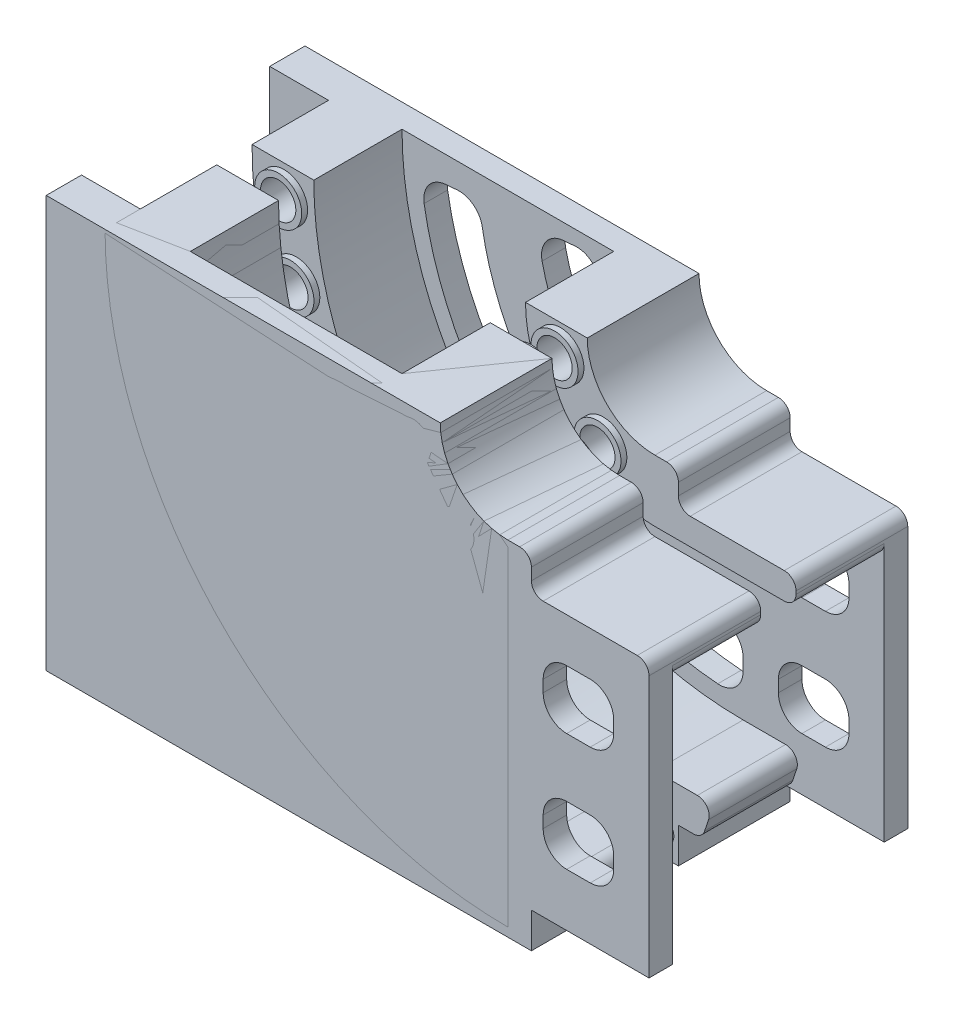
SolidWorks part; units mm, degrees
ref_plane "前视基准面" through (0, 0, 0) normal (0, 0, 1) x (1, 0, 0)
ref_plane "上视基准面" through (0, 0, 0) normal (0, 1, 0) x (1, 0, 0)
ref_plane "右视基准面" through (0, 0, 0) normal (1, 0, 0) x (0, 0, -1)
other "Configuration Table"
sketch "草图1" plane through (0, 0, 0) normal (0, 0, 1) x (1, 0, 0)
  line L0 (0, 0) -> (0, -1)
  arc A0 (0, -1) -> (20, -21) centre (20, -1) ccw
  dimension "D1" = 20
  dimension "D2" = 1
sketch "草图2" plane through (0, 0, 0) normal (0, 1, 0) x (1, 0, 0)
  line L1 (-9, -9) -> (9, -9)
  line L2 (-9, -9) -> (-9, 9)
  line L3 (-9, 9) -> (9, 9)
  line L4 (9, -9) -> (9, 9)
  line L5 (-9, -9) -> (9, 9) construction
  line L6 (-9, 9) -> (9, -9) construction
  line L7 (-14.25, -11) -> (14.25, -11)
  line L8 (-14.25, -11) -> (-14.25, 11)
  line L9 (-14.25, 11) -> (14.25, 11)
  line L10 (14.25, -11) -> (14.25, 11)
  line L11 (-14.25, -11) -> (14.25, 11) construction
  line L12 (-14.25, 11) -> (14.25, -11) construction
  point P0 (0, 0)
  point P6 (0, 0)
  dimension "D1" = 2
  dimension "D2" = 18
  dimension "D3" = 5.25
sweep "扫描1" add profiles "草图2" path "草图1"
sketch "草图3" plane through (0, 0, 0) normal (0, 1, 0) x (1, 0, 0)
  line L1 (-16.4922, 1.5) -> (34.5235, 1.5)
  line L2 (-16.4922, 1.5) -> (-16.4922, -1.5)
  line L3 (-16.4922, -1.5) -> (34.5235, -1.5)
  line L4 (34.5235, 1.5) -> (34.5235, -1.5)
  dimension "D1" = 3
  dimension "1" = 1.5
extrude "切除-拉伸1" cut sketch "草图3" against normal blind 50
sketch "草图5" plane through (0, 0, -1.5) normal (0, 0, 1) x (1, 0, 0)
  line L0 (20, -12) -> (20, -6.75) construction
  line L1 (12.1, 0) -> (-12.1, 0) construction
  line L2 (20, -35.25) -> (20, -30) construction
  line L3 (-11.625, -1) -> (-11.625, 0) construction
  line L8 (14.25, 0) -> (9, 0)
  line L9 (9, 0) -> (9, -1)
  line L10 (20, -12) -> (20, -6.75)
  line L11 (14.25, -1) -> (14.25, 0)
  line L12 (14.25, 0) -> (9, 0)
  line L13 (9, 0) -> (9, -1)
  line L14 (20, -12) -> (20, -6.75)
  line L15 (14.25, -1) -> (14.25, 0)
  line L16 (20, -35.25) -> (20, -30)
  line L17 (-9, -1) -> (-9, 0)
  line L18 (-9, 0) -> (-14.25, 0)
  line L19 (-14.25, 0) -> (-14.25, -1)
  line L20 (20, -35.25) -> (20, -30)
  line L21 (-9, -1) -> (-9, 0)
  line L22 (-9, 0) -> (-14.25, 0)
  line L23 (-14.25, 0) -> (-14.25, -1)
  arc A0 (20, -9.375) -> (11.6849, 0) centre (20, -1) cw construction
  arc A1 (14.25, -1) -> (20, -6.75) centre (20, -1) ccw construction
  arc A2 (20, -32.625) -> (-11.625, -1) centre (20, -1) cw construction
  circle A3 centre (11.9674, -3.3702) radius 3 construction
  circle A4 centre (15.6141, -8.1348) radius 3 construction
  circle A5 centre (21.5119, -9.2374) radius 3 construction
  circle A6 centre (26.6337, -6.1121) radius 3 construction
  circle A7 centre (28.3507, -0.3631) radius 3 construction
  circle A8 centre (11.9674, -3.3702) radius 1.5
  circle A9 centre (15.6141, -8.1348) radius 1.5
  circle A10 centre (21.5119, -9.2374) radius 1.5
  circle A11 centre (26.6337, -6.1121) radius 1.5
  circle A12 centre (28.3507, -0.3631) radius 1.5
  circle A13 centre (-11.5273, -3.484) radius 3 construction
  circle A14 centre (-10.4907, -9.3938) radius 3 construction
  circle A15 centre (-8.3567, -15.0014) radius 3 construction
  circle A16 centre (-5.2019, -20.1051) radius 3 construction
  circle A17 centre (-1.14, -24.5211) radius 3 construction
  circle A18 centre (3.6829, -28.0904) radius 3 construction
  circle A19 centre (9.093, -30.6847) radius 3 construction
  circle A20 centre (14.8958, -32.2104) radius 3 construction
  circle A21 centre (20.8823, -32.6127) radius 3 construction
  circle A22 centre (26.837, -31.8771) radius 3 construction
  circle A23 centre (32.5457, -30.0301) radius 3 construction
  circle A24 centre (-11.5273, -3.484) radius 1.5
  circle A25 centre (-10.4907, -9.3938) radius 1.5
  arc A26 (9, -1) -> (20, -12) centre (20, -1) ccw
  arc A27 (14.25, -1) -> (20, -6.75) centre (20, -1) ccw
  arc A28 (9, -1) -> (20, -12) centre (20, -1) ccw
  arc A29 (14.25, -1) -> (20, -6.75) centre (20, -1) ccw
  arc A30 (-14.25, -1) -> (20, -35.25) centre (20, -1) ccw
  arc A31 (-9, -1) -> (20, -30) centre (20, -1) ccw
  arc A32 (-14.25, -1) -> (20, -35.25) centre (20, -1) ccw
  arc A33 (-9, -1) -> (20, -30) centre (20, -1) ccw
  circle A34 centre (-8.3567, -15.0014) radius 1.5
  circle A35 centre (-5.2019, -20.1051) radius 1.5
  circle A36 centre (-1.14, -24.5211) radius 1.5
  circle A37 centre (3.6829, -28.0904) radius 1.5
  circle A38 centre (9.093, -30.6847) radius 1.5
  circle A39 centre (14.8958, -32.2104) radius 1.5
  circle A40 centre (20.8823, -32.6127) radius 1.5
  circle A41 centre (26.837, -31.8771) radius 1.5
  circle A42 centre (32.5457, -30.0301) radius 1.5
  circle A43 centre (11.9674, -3.3702) radius 2
  circle A44 centre (15.6141, -8.1348) radius 2
  circle A45 centre (21.5119, -9.2374) radius 2
  circle A46 centre (26.6337, -6.1121) radius 2
  circle A47 centre (28.3507, -0.3631) radius 2
  circle A48 centre (32.5457, -30.0301) radius 2
  circle A49 centre (26.837, -31.8771) radius 2
  circle A50 centre (20.8823, -32.6127) radius 2
  circle A51 centre (14.8958, -32.2104) radius 2
  circle A52 centre (9.093, -30.6847) radius 2
  circle A53 centre (3.6829, -28.0904) radius 2
  circle A54 centre (-1.14, -24.5211) radius 2
  circle A55 centre (-5.2019, -20.1051) radius 2
  circle A56 centre (-8.3567, -15.0014) radius 2
  circle A57 centre (-10.4907, -9.3938) radius 2
  circle A58 centre (-11.5273, -3.484) radius 2
  dimension "D1" = 6
  dimension "D4" = 3
  dimension "D5" = 4
  dimension "D2" = 0
  dimension "D3" = 0
extrude "凸台-拉伸1" add sketch "草图5" along normal blind 0.5 contours A58 A24 | A43 A8 | A44 A9 | A51 A39 | A52 A38 | A53 A37 | A54 A36 | A55 A35 | A56 A34 | A57 A25 | A12
sketch "草图7" plane through (0, 0, -1.5) normal (0, 0, 1) x (1, 0, 0)
  circle A0 centre (11.9674, -3.3702) radius 1.5 construction
  circle A1 centre (15.6141, -8.1348) radius 1.5 construction
  circle A8 centre (14.8958, -32.2104) radius 1.5 construction
  circle A9 centre (9.093, -30.6847) radius 1.5 construction
  circle A10 centre (3.6829, -28.0904) radius 1.5 construction
  circle A11 centre (-1.14, -24.5211) radius 1.5 construction
  circle A12 centre (-5.2019, -20.1051) radius 1.5 construction
  circle A13 centre (-8.3567, -15.0014) radius 1.5 construction
  circle A14 centre (-10.4907, -9.3938) radius 1.5 construction
  circle A15 centre (-11.5273, -3.484) radius 1.5 construction
  circle A16 centre (11.9674, -3.3702) radius 1.5
  circle A17 centre (15.6141, -8.1348) radius 1.5
  circle A24 centre (14.8958, -32.2104) radius 1.5
  circle A25 centre (9.093, -30.6847) radius 1.5
  circle A26 centre (3.6829, -28.0904) radius 1.5
  circle A27 centre (-1.14, -24.5211) radius 1.5
  circle A28 centre (-5.2019, -20.1051) radius 1.5
  circle A29 centre (-8.3567, -15.0014) radius 1.5
  circle A30 centre (-10.4907, -9.3938) radius 1.5
  circle A31 centre (-11.5273, -3.484) radius 1.5
extrude "切除-拉伸3" cut sketch "草图7" against normal blind 10
sketch "草图18" plane through (20, 0, 0) normal (1, 0, 0) x (0, 0, -1)
  line L8 (1.5, -30) -> (1.5, -35.25)
  line L9 (1.5, -35.25) -> (11, -35.25)
  line L11 (11, -6.75) -> (1.5, -6.75)
  line L12 (1.5, -6.75) -> (1.5, -12)
  line L13 (1.5, -12) -> (9, -12)
  line L14 (9, -12) -> (9, -30)
  line L15 (9, -30) -> (1.5, -30)
  line L16 (1.5, -30) -> (1.5, -35.25)
  line L19 (11, -6.75) -> (1.5, -6.75)
  line L20 (1.5, -6.75) -> (1.5, -12)
  line L21 (1.5, -12) -> (9, -12)
  line L22 (9, -12) -> (9, -30)
  line L23 (9, -30) -> (1.5, -30)
  line L25 (1.5, -35.25) -> (11, -35.25)
  line L26 (11, -35.25) -> (11, -6.75)
  line L28 (11, -35.25) -> (11, -6.75)
  dimension "D1" = 0
extrude "凸台-拉伸3" add sketch "草图18" along normal blind 2
sketch "草图19" plane through (0, 0, -11) normal (0, 0, -1) x (-1, 0, 0)
  line L0 (14.25, 0) -> (19.25, 0)
  line L5 (-22, -30) -> (-20, -30) construction
  line L6 (-22, -30) -> (-20, -30)
  line L7 (-22, -30) -> (-22, -36)
  line L8 (-22, -36) -> (19.25, -36)
  line L9 (19.25, 0) -> (19.25, -36)
  line L10 (12.1, 0) -> (-12.1, 0) construction
  line L11 (14.25, 0) -> (14.25, -1) construction
  line L12 (14.25, -1) -> (14.25, 0)
  line L13 (14.25, -1) -> (-14.25, -1)
  line L14 (-20, -6.75) -> (-22, -6.75)
  line L15 (-22, -6.75) -> (-22, -35.25)
  line L16 (-22, -35.25) -> (-20, -35.25)
  line L17 (14.25, -1) -> (-14.25, -1)
  line L18 (-20, -6.75) -> (-22, -6.75)
  line L19 (-22, -6.75) -> (-22, -35.25)
  line L20 (-22, -35.25) -> (-20, -35.25)
  arc A2 (-20, -35.25) -> (14.25, -1) centre (-20, -1) ccw
  arc A3 (-20, -6.75) -> (-14.25, -1) centre (-20, -1) ccw
  arc A4 (-20, -35.25) -> (14.25, -1) centre (-20, -1) ccw
  arc A5 (-20, -6.75) -> (-14.25, -1) centre (-20, -1) ccw
  dimension "D1" = 6
  dimension "D2" = 0
  dimension "D3" = 5
extrude "凸台-拉伸4" add sketch "草图19" against normal blind 3
sketch "草图21" plane through (0, 0, -8) normal (0, 0, 1) x (1, 0, 0)
  line L0 (-19.25, -26) -> (-3.4107, -26)
  line L5 (-14.25, -1) -> (-14.25, 0)
  line L7 (-14.25, -1) -> (-14.25, 0)
  line L9 (-14.25, 0) -> (-19.25, 0)
  line L10 (22, -36) -> (22, -35.25)
  line L16 (22, -36) -> (22, -35.25)
  line L20 (-14.25, 0) -> (-19.25, 0)
  line L21 (-19.25, 0) -> (-19.25, -36)
  line L22 (-19.25, 0) -> (-19.25, -36)
  line L23 (-19.25, -36) -> (22, -36)
  line L24 (-19.25, -36) -> (22, -36)
  line L25 (22, -35.25) -> (20, -35.25)
  line L26 (22, -35.25) -> (20, -35.25)
  arc A1 (-14.25, -1) -> (20, -35.25) centre (20, -1) ccw
  arc A3 (-14.25, -1) -> (20, -35.25) centre (20, -1) ccw
  dimension "D1" = 0
extrude "凸台-拉伸5" add sketch "草图21" along normal up to surface (6.5 mm away) up to face at (13.6141, -8.1348, -1.5)
sketch "草图22" plane through (0, -36, 0) normal (0, -1, 0) x (1, 0, 0)
  line L0 (22, -6.25) -> (-14.25, -6.25) construction
  line L1 (22, -1.5) -> (22, -11) construction
  line L2 (-19.25, -1.5) -> (-19.25, -11) construction
  circle A1 centre (5.75, -6.25) radius 1.25
  circle A2 centre (-14.25, -6.25) radius 1.25
  dimension "D1" = 20
  dimension "D2" = 5
  dimension "D3" = 2.5
extrude "切除-拉伸8" cut sketch "草图22" against normal blind 6
mirror "镜向1" about plane through (0, 0, 0) normal (0, 0, 1) of bodies 125 121
sketch "草图27" plane through (0, 0, 0) normal (0, 1, 0) x (1, 0, 0)
  line L0 (14.25, -11) -> (-19.25, -11) construction
  line L1 (9, 9) -> (14.25, 9)
  line L2 (9, 9) -> (9, 11)
  line L3 (9, 11) -> (14.25, 11)
  line L4 (14.25, 9) -> (14.25, 11)
  line L5 (9, -9) -> (14.25, -9)
  line L6 (9, -9) -> (9, -11)
  line L7 (9, -11) -> (14.25, -11)
  line L8 (14.25, -9) -> (14.25, -11)
  line L9 (-9, -9) -> (-19.25, -9)
  line L10 (-9, -9) -> (-9, -11)
  line L11 (-9, -11) -> (-19.25, -11)
  line L12 (-19.25, -9) -> (-19.25, -11)
  line L13 (14.25, 11) -> (-19.25, 11) construction
  line L14 (-9, 9) -> (-19.25, 9)
  line L15 (-9, 9) -> (-9, 11)
  line L16 (-9, 11) -> (-19.25, 11)
  line L17 (-19.25, 9) -> (-19.25, 11)
  line L21 (-19.25, -8) -> (-19.25, -11) construction
  line L22 (-19.25, 8) -> (-19.25, 11) construction
sketch "草图31" plane through (22, 0, 0) normal (1, 0, 0) x (0, 0, -1)
  line L0 (9, -30) -> (1.5, -30) construction
  line L1 (1.5, -30) -> (1.5, -36) construction
  line L2 (1.5, -36) -> (11, -36) construction
  line L3 (11, -36) -> (11, -6.75) construction
  line L4 (11, -6.75) -> (1.5, -6.75) construction
  line L5 (1.5, -6.75) -> (1.5, -12) construction
  line L6 (1.5, -12) -> (9, -12) construction
  line L7 (9, -12) -> (9, -30) construction
  line L8 (-1.5, -30) -> (-9, -30) construction
  line L9 (-9, -30) -> (-9, -12) construction
  line L10 (-9, -12) -> (-1.5, -12) construction
  line L11 (-1.5, -12) -> (-1.5, -6.75) construction
  line L12 (-1.5, -6.75) -> (-11, -6.75) construction
  line L13 (-11, -6.75) -> (-11, -36) construction
  line L14 (-11, -36) -> (-1.5, -36) construction
  line L15 (-1.5, -36) -> (-1.5, -30) construction
  line L16 (9, -30) -> (1.5, -30)
  line L17 (1.5, -30) -> (1.5, -36)
  line L18 (1.5, -36) -> (11, -36)
  line L19 (11, -36) -> (11, -6.75)
  line L20 (11, -6.75) -> (1.5, -6.75)
  line L21 (1.5, -6.75) -> (1.5, -12)
  line L22 (1.5, -12) -> (9, -12)
  line L23 (9, -12) -> (9, -30)
  line L24 (-1.5, -30) -> (-9, -30)
  line L25 (-9, -30) -> (-9, -12)
  line L26 (-9, -12) -> (-1.5, -12)
  line L27 (-1.5, -12) -> (-1.5, -6.75)
  line L28 (-1.5, -6.75) -> (-11, -6.75)
  line L29 (-11, -6.75) -> (-11, -36)
  line L30 (-11, -36) -> (-1.5, -36)
  line L31 (-1.5, -36) -> (-1.5, -30)
extrude "凸台-拉伸12" add sketch "草图31" along normal blind 10
sketch "草图32" plane through (0, 0, 11) normal (0, 0, 1) x (1, 0, 0)
  line L0 (32, -36) -> (-19.25, -36) construction
  line L5 (22, -36) -> (32, -36)
  line L11 (22, -36) -> (22, -33)
  line L12 (32, -6.75) -> (20, -6.75) construction
  line L13 (22, -6.75) -> (32, -6.75)
  line L14 (22, -6.75) -> (22, -9.75)
  line L15 (22, -9.75) -> (32, -9.75)
  line L16 (32, -6.75) -> (32, -9.75)
  line L17 (32, -6.75) -> (32, -36) construction
  line L18 (22, -33) -> (32, -33)
  line L19 (32, -36) -> (32, -33)
  dimension "D1" = 10
  dimension "D2" = 3
  dimension "D3" = 3
  dimension "D4" = 10
extrude "切除-拉伸11" cut sketch "草图32" against normal blind 30
sketch "草图34" plane through (0, 0, 11) normal (0, 0, 1) x (1, 0, 0)
  line L0 (14.25, -1) -> (-14.25, -1) construction
  line L1 (20, -1) -> (-7.3954, -3.3968)
  line L2 (20, -1) -> (20, -28.5)
  line L5 (23, -1) -> (23, -30.3246)
  line L6 (29, -1) -> (29, -30.0257)
  line L7 (32, -9.75) -> (32, -33) construction
  line L8 (20, -13.5) -> (29, -13.5)
  line L9 (20, -18.5) -> (29, -18.5)
  line L10 (20, -23.5) -> (29, -23.5)
  line L11 (20, -28.5) -> (29, -28.5)
  line L12 (20, -1) -> (-2.5267, -16.7734)
  line L13 (20, -1) -> (4.2266, -23.5267)
  line L14 (20, -1) -> (0, -1) construction
  arc A0 (14.25, -1) -> (20, -6.75) centre (20, -1) ccw construction
  arc A1 (14.25, -1) -> (20, -6.75) centre (20, -1) ccw construction
  arc A2 (7.5, -1) -> (20, -13.5) centre (20, -1) ccw
  arc A3 (2.5, -1) -> (20, -18.5) centre (20, -1) ccw
  arc A4 (-2.5, -1) -> (20, -23.5) centre (20, -1) ccw
  arc A5 (-7.3954, -3.3968) -> (20, -28.5) centre (20, -1) ccw
  arc A6 (-11.5273, -3.484) -> (14.8948, -32.2102) centre (20, -1) ccw construction
  arc A7 (0, -1) -> (20, -21) centre (20, -1) ccw construction
  dimension "D1" = 5
  dimension "D2" = 5
  dimension "D3" = 2.5
  dimension "D4" = 5
  dimension "D5" = 3
  dimension "D6" = 3
  dimension "D7" = 5
  dimension "D8" = 35
  dimension "D9" = 30
extrude "切除-拉伸13" cut sketch "草图34" against normal through all both and the other way through all contours L1 A3 L12 A2 | L1 A5 L12 A4 | L13 A5 L2 A4 | L13 A3 L2 A2 | L5 L9 L6 L8 | L5 L11 L6 L10
fillet "圆角8" radius 2 24 edges at (29, -28.5, 10) (29, -23.5, 10) (23, -23.5, 10) (23, -28.5, 10) (29, -18.5, 10) (29, -13.5, 10) (23, -13.5, 10) (23, -18.5, 10)
fillet "圆角9" radius 2 24 edges at (9.7606, -8.1697, -10) (5.6648, -11.0376, -10) (1.5691, -13.9055, -10) (-2.5267, -16.7734, -10) (-7.3954, -3.3968, -10) (-2.4144, -2.961, -10) (2.5666, -2.5252, -10) (7.5476, -2.0894, -10) (29, -23.5, -10) (29, -28.5, -10) (23, -28.5, -10) (23, -23.5, -10) (29, -13.5, -10) (29, -18.5, -10) (23, -18.5, -10) (23, -13.5, -10) (20, -13.5, -10) (9.9624, -15.3352, -10) (12.8303, -11.2394, -10) (20, -23.5, -10) (20, -28.5, -10) (4.2266, -23.5267, -10) (7.0945, -19.4309, -10) (20, -18.5, -10)
fillet "圆角10" radius 1 7 edges at (14.25, 0, -6.25) (32, -12, -5.25) (32, -9.75, -6.25) (22, -9.75, -6.25) (22, -6.75, -6.25) (14.25, -0.5, -11) (14.25, -0.5, -1.5)
fillet "圆角11" radius 1 1 edges at (14.25, 0, 6.25)
fillet "圆角12" radius 1 10 edges at (9, 0, 5.25) (14.25, 0, 6.25) (32, -12, 5.25) (9, -0.5, 1.5) (9, -0.5, 9) (32, -9.75, 6.25) (22, -9.75, 6.25) (22, -6.75, 6.25) (14.25, -0.5, 11) (14.25, -0.5, 1.5)
sketch "草图36" plane through (0, 0, -11) normal (0, 0, -1) x (-1, 0, 0)
  line L1 (19.25, 0) -> (-18.4022, 0)
  line L2 (19.25, 0) -> (19.25, -1)
  line L3 (19.25, -1) -> (-18.4022, -1)
  line L4 (-18.4022, 0) -> (-18.4022, -1)
  dimension "D1" = 1
extrude "切除-拉伸14" cut sketch "草图36" against normal through all
sketch "草图37" plane through (0, -1, 0) normal (0, 1, 0) x (1, 0, 0)
  circle A0 centre (0, 0) radius 9
extrude "凸台-拉伸13" [suppressed] add sketch "草图37" along normal blind 1
sketch "草图39" plane through (0, 0, -9) normal (0, 0, 1) x (1, 0, 0)
  line L0 (32, -30) -> (25, -30)
  line L1 (25, -30) -> (24, -33)
  line L2 (32, -33) -> (22, -33) construction
  line L3 (24, -33) -> (32, -33)
  line L4 (32, -10.75) -> (32, -33) construction
  line L5 (32, -33) -> (32, -30)
  dimension "D1" = 7
  dimension "D2" = 8
extrude "切除-拉伸15" cut sketch "草图39" along normal up to surface (18 mm away)
fillet "圆角13" radius 1 2 edges at (24, -33, 5.25) (25, -30, 5.25)
fillet "圆角14" radius 1 2 edges at (24, -33, -5.25) (25, -30, -5.25)
sketch "草图40" plane through (0, 0, -11) normal (0, 0, -1) x (-1, 0, 0)
  line L0 (9.625, -1) -> (13.625, -1)
  line L1 (-20, -30.625) -> (-20, -34.625)
  arc A0 (-20, -32.625) -> (11.625, -1) centre (-20, -1) ccw construction
  arc A1 (-20, -34.625) -> (13.625, -1) centre (-20, -1) ccw
  arc A2 (-20, -30.625) -> (9.625, -1) centre (-20, -1) ccw
  circle A3 centre (-20, -1) radius 33.625 construction
  circle A4 centre (-20, -1) radius 31.625 construction
  circle A5 centre (-20, -1) radius 29.625 construction
  dimension "D1" = 2
  dimension "D2" = 2
extrude "凸台-拉伸14" add sketch "草图40" against normal blind 3
sketch "草图41" plane through (0, 0, 11) normal (0, 0, 1) x (1, 0, 0)
  line L2 (-9.625, -1) -> (-13.625, -1)
  line L3 (20, -34.625) -> (20, -30.625)
  line L4 (-9.625, -1) -> (-13.625, -1)
  line L5 (20, -34.625) -> (20, -30.625)
  line L9 (14.25, -1) -> (-19.25, -1)
  line L10 (-19.25, -1) -> (-19.25, -36)
  line L11 (-19.25, -36) -> (22, -36)
  line L12 (22, -36) -> (22, -33)
  line L13 (22, -33) -> (32, -33)
  line L14 (32, -33) -> (32, -10.75)
  line L15 (31, -9.75) -> (23, -9.75)
  line L16 (22, -8.75) -> (22, -7.75)
  line L17 (21, -6.75) -> (20, -6.75)
  line L18 (14.25, -1) -> (-19.25, -1)
  line L19 (-19.25, -1) -> (-19.25, -36)
  line L20 (-19.25, -36) -> (22, -36)
  line L21 (22, -36) -> (22, -33)
  line L22 (22, -33) -> (32, -33)
  line L23 (32, -33) -> (32, -10.75)
  line L24 (31, -9.75) -> (23, -9.75)
  line L25 (22, -8.75) -> (22, -7.75)
  line L26 (21, -6.75) -> (20, -6.75)
  arc A2 (-13.625, -1) -> (20, -34.625) centre (20, -1) ccw
  arc A3 (-9.625, -1) -> (20, -30.625) centre (20, -1) ccw
  arc A4 (32, -10.75) -> (31, -9.75) centre (31, -10.75) ccw
  arc A5 (22, -8.75) -> (23, -9.75) centre (23, -8.75) ccw
  arc A6 (22, -7.75) -> (21, -6.75) centre (21, -7.75) ccw
  arc A7 (14.25, -1) -> (20, -6.75) centre (20, -1) ccw
  arc A8 (32, -10.75) -> (31, -9.75) centre (31, -10.75) ccw
  arc A9 (22, -8.75) -> (23, -9.75) centre (23, -8.75) ccw
  arc A10 (22, -7.75) -> (21, -6.75) centre (21, -7.75) ccw
  arc A11 (14.25, -1) -> (20, -6.75) centre (20, -1) ccw
  arc A12 (-13.625, -1) -> (20, -34.625) centre (20, -1) ccw
  arc A13 (-9.625, -1) -> (20, -30.625) centre (20, -1) ccw
  dimension "D1" = 0
  dimension "D2" = 0
extrude "凸台-拉伸15" add sketch "草图41" against normal blind 3 contours A13 L4 A12 L5
